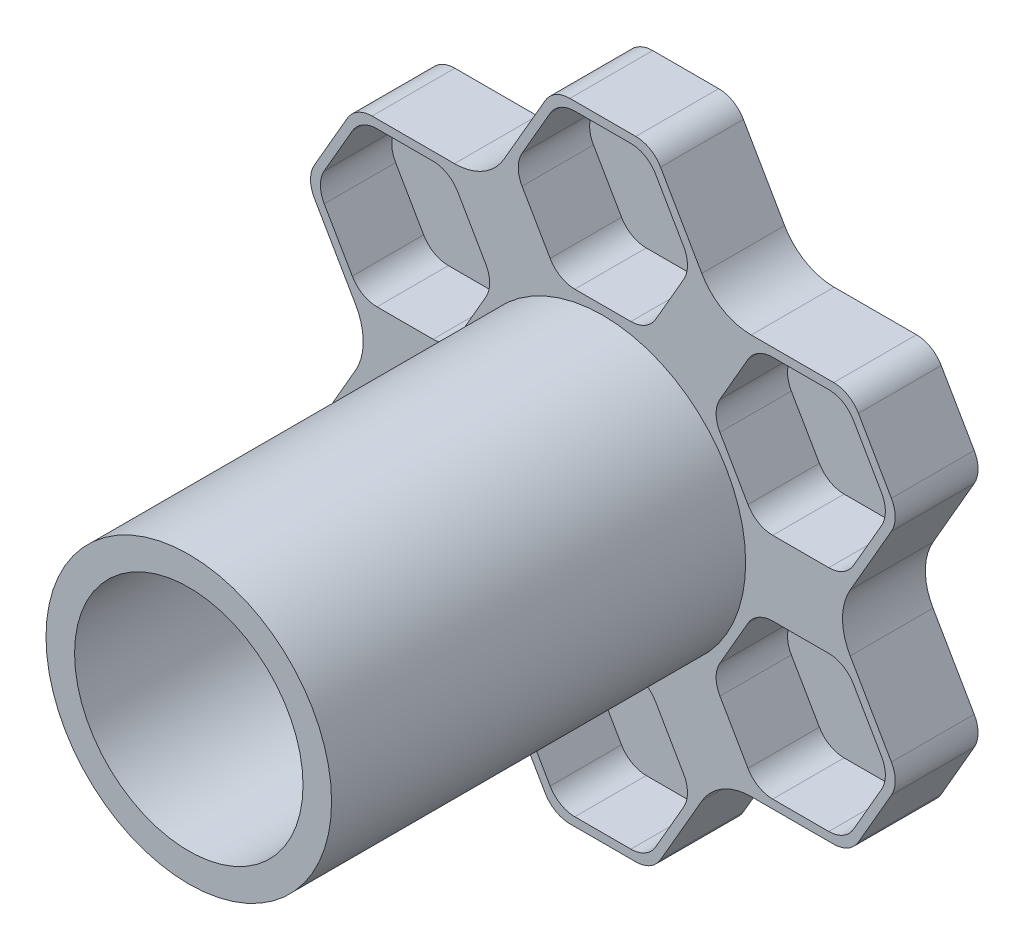
SolidWorks part; units mm, degrees
note: The reader was unsure of these and kept them because the rebuilt part matched: shared geometry of "Base_Sketch<3>", "Base_Sketch<4>", "Base_Sketch<5>", "Base_Sketch<7>".
ref_plane "Front Plane" through (0, 0, 0) normal (0, 0, 1) x (1, 0, 0)
ref_plane "Top Plane" through (0, 0, 0) normal (0, 1, 0) x (1, 0, 0)
ref_plane "Right Plane" through (0, 0, 0) normal (1, 0, 0) x (0, 0, -1)
sketch "Base_Sketch" plane through (0, 0, 0) normal (0, 0, 1) x (1, 0, 0)
  line L0 (0, 38.7616) -> (0, -17.7739) construction
  line L1 (-17.446, 0) -> (12.0679, 0) construction
  line L2 (-15.5885, 107) -> (-31.1769, 80)
  line L3 (34.641, 80) -> (17.3205, 110)
  line L4 (17.3205, 110) -> (-17.3205, 110)
  line L5 (-17.3205, 110) -> (-34.641, 80)
  line L6 (-34.641, 80) -> (-17.3205, 50)
  line L7 (-17.3205, 50) -> (17.3205, 50)
  line L8 (17.3205, 50) -> (34.641, 80)
  line L9 (-31.1769, 80) -> (-15.5885, 53)
  line L10 (-15.5885, 53) -> (15.5885, 53)
  line L11 (15.5885, 53) -> (31.1769, 80)
  line L12 (31.1769, 80) -> (15.5885, 107)
  line L13 (15.5885, 107) -> (-15.5885, 107)
  line L14 (51.9615, 70) -> (34.641, 40)
  line L15 (53.6936, 67) -> (38.1051, 40)
  line L16 (34.641, 40) -> (51.9615, 10)
  line L17 (51.9615, 10) -> (86.6025, 10)
  line L18 (86.6025, 10) -> (103.923, 40)
  line L19 (53.6936, 13) -> (84.8705, 13)
  line L20 (38.1051, 40) -> (53.6936, 13)
  line L21 (84.8705, 67) -> (53.6936, 67)
  line L22 (100.4589, 40) -> (84.8705, 67)
  line L23 (84.8705, 13) -> (100.4589, 40)
  line L24 (103.923, 40) -> (86.6025, 70)
  line L25 (86.6025, 70) -> (51.9615, 70)
  line L26 (86.6025, -10) -> (51.9615, -10)
  line L27 (84.8705, -13) -> (53.6936, -13)
  line L28 (51.9615, -10) -> (34.641, -40)
  line L29 (34.641, -40) -> (51.9615, -70)
  line L30 (51.9615, -70) -> (86.6025, -70)
  line L31 (38.1051, -40) -> (53.6936, -67)
  line L32 (53.6936, -13) -> (38.1051, -40)
  line L33 (100.4589, -40) -> (84.8705, -13)
  line L34 (84.8705, -67) -> (100.4589, -40)
  line L35 (53.6936, -67) -> (84.8705, -67)
  line L36 (86.6025, -70) -> (103.923, -40)
  line L37 (103.923, -40) -> (86.6025, -10)
  line L38 (34.641, -80) -> (17.3205, -50)
  line L39 (31.1769, -80) -> (15.5885, -53)
  line L40 (17.3205, -50) -> (-17.3205, -50)
  line L41 (-17.3205, -50) -> (-34.641, -80)
  line L42 (-34.641, -80) -> (-17.3205, -110)
  line L43 (-15.5885, -53) -> (-31.1769, -80)
  line L44 (15.5885, -53) -> (-15.5885, -53)
  line L45 (15.5885, -107) -> (31.1769, -80)
  line L46 (-15.5885, -107) -> (15.5885, -107)
  line L47 (-31.1769, -80) -> (-15.5885, -107)
  line L48 (-17.3205, -110) -> (17.3205, -110)
  line L49 (17.3205, -110) -> (34.641, -80)
  line L50 (-51.9615, -70) -> (-34.641, -40)
  line L51 (-53.6936, -67) -> (-38.1051, -40)
  line L52 (-34.641, -40) -> (-51.9615, -10)
  line L53 (-51.9615, -10) -> (-86.6025, -10)
  line L54 (-86.6025, -10) -> (-103.923, -40)
  line L55 (-53.6936, -13) -> (-84.8705, -13)
  line L56 (-38.1051, -40) -> (-53.6936, -13)
  line L57 (-84.8705, -67) -> (-53.6936, -67)
  line L58 (-100.4589, -40) -> (-84.8705, -67)
  line L59 (-84.8705, -13) -> (-100.4589, -40)
  line L60 (-103.923, -40) -> (-86.6025, -70)
  line L61 (-86.6025, -70) -> (-51.9615, -70)
  line L62 (-86.6025, 10) -> (-51.9615, 10)
  line L63 (-84.8705, 13) -> (-53.6936, 13)
  line L64 (-51.9615, 10) -> (-34.641, 40)
  line L65 (-34.641, 40) -> (-51.9615, 70)
  line L66 (-51.9615, 70) -> (-86.6025, 70)
  line L67 (-38.1051, 40) -> (-53.6936, 67)
  line L68 (-53.6936, 13) -> (-38.1051, 40)
  line L69 (-100.4589, 40) -> (-84.8705, 13)
  line L70 (-84.8705, 67) -> (-100.4589, 40)
  line L71 (-53.6936, 67) -> (-84.8705, 67)
  line L72 (-86.6025, 70) -> (-103.923, 40)
  line L73 (-103.923, 40) -> (-86.6025, 10)
  circle A0 centre (0, 0) radius 50
  circle A1 centre (0, 80) radius 30 construction
  arc A3 (34.641, 80) -> (51.9615, 70) centre (51.9615, 90) ccw
  circle A4 centre (69.282, 40) radius 30 construction
  arc A5 (86.6025, 10) -> (86.6025, -10) centre (103.923, 0) ccw
  circle A6 centre (69.282, -40) radius 30 construction
  arc A7 (51.9615, -70) -> (34.641, -80) centre (51.9615, -90) ccw
  circle A8 centre (0, -80) radius 30 construction
  arc A9 (-34.641, -80) -> (-51.9615, -70) centre (-51.9615, -90) ccw
  circle A10 centre (-69.282, -40) radius 30 construction
  arc A11 (-86.6025, -10) -> (-86.6025, 10) centre (-103.923, 0) ccw
  circle A12 centre (-69.282, 40) radius 30 construction
  arc A13 (-51.9615, 70) -> (-34.641, 80) centre (-51.9615, 90) ccw
  circle A14 centre (0, 0) radius 40
  circle A15 centre (0, 0) radius 10
  point P18 (0, 50)
  point P36 (43.3013, 25)
  point P53 (43.3013, -25)
  point P70 (0, -50)
  point P87 (-43.3013, -25)
  point P104 (-43.3013, 25)
  point P111 (0, 0)
  dimension "D1" = 100
  dimension "D3" = 60
  dimension "D5" = 10
  dimension "D6" = 20
  dimension "D2" = 3
  dimension "D4" = 6
extrude "Boss-Extrude2" add sketch "Base_Sketch" against normal blind 4 contours L55 L59 L58 L57 L51 L56 | L31 L35 L34 L33 L27 L32 | L43 L47 L46 L45 L39 L44 | A7 L29 L28 A0 L40 L38 | L48 L49 L38 L40 L41 L42 L47 L43 L44 L39 L45 L46 | L36 L37 L26 L28 L29 L30 L35 L31 L32 L27 L33 L34 | A5 L17 L16 A0 L28 L26 | L24 L25 L14 L16 L17 L18 L23 L19 L20 L15 L21 L22 | L19 L23 L22 L21 L15 L20 | L12 L13 L2 L9 L10 L11 | L7 L8 L3 L4 L5 L6 L13 L12 L11 L10 L9 L2 | L72 L73 L62 L64 L65 L66 L71 L67 L68 L63 L69 L70 | A13 L65 L64 A0 L7 L6 | A11 L53 L52 A0 L64 L62 | A9 L41 L40 A0 L52 L50 | L60 L61 L50 L52 L53 L54 L59 L55 L56 L51 L57 L58 | L67 L71 L70 L69 L63 L68 | A3 L8 L7 A0 L16 L14
extrude "Boss-Extrude3" add sketch "Base_Sketch<3>" along normal blind 25 from surface at 0 contours A0 A14 | A15 | L60 L61 L50 L52 L53 L54 L59 L55 L56 L51 L57 L58 | A9 L41 L40 A0 L52 L50 | L48 L49 L38 L40 L41 L42 L47 L43 L44 L39 L45 L46 | A7 L29 L28 A0 L40 L38 | L31 L35 L34 L33 L27 L32 | L36 L37 L26 L28 L29 L30 L35 L31 L32 L27 L33 L34 | A5 L17 L16 A0 L28 L26 | L24 L25 L14 L16 L17 L18 L23 L19 L20 L15 L21 L22 | A3 L8 L7 A0 L16 L14 | L7 L8 L3 L4 L5 L6 L13 L12 L11 L10 L9 L2 | A13 L65 L64 A0 L7 L6 | L72 L73 L62 L64 L65 L66 L71 L67 L68 L63 L69 L70 | A11 L53 L52 A0 L64 L62 | A14 A15
sketch "Base_Sketch<3>" plane through (0, 0, 0) normal (0, 0, 1) x (1, 0, 0) same geometry as "Base_Sketch"
extrude "Boss-Extrude4" add sketch "Base_Sketch<4>" along normal blind 40 from surface at 25 contours A0 A14 | A14 A15 | A15 starting at face at (69.282, -40, 25)
sketch "Base_Sketch<4>" plane through (0, 0, 0) normal (0, 0, 1) x (1, 0, 0) same geometry as "Base_Sketch"
extrude "Boss-Extrude5" add sketch "Base_Sketch<5>" along normal blind 5 from surface at 65 contours A0 A14 | A14 A15 | A15 starting at face at (50, 0, 65)
sketch "Base_Sketch<5>" plane through (0, 0, 0) normal (0, 0, 1) x (1, 0, 0) same geometry as "Base_Sketch"
extrude "Boss-Extrude6" add sketch "Base_Sketch<7>" along normal blind 100 from surface at 70 contours A0 A14 starting at face at (50, 0, 70)
sketch "Base_Sketch<7>" plane through (0, 0, 0) normal (0, 0, 1) x (1, 0, 0) same geometry as "Base_Sketch"
fillet "Fillet1" radius 10 8 edges at (-31.1769, 80, 12.5) (-15.5885, 53, 12.5) (15.5885, 53, 12.5) (17.3205, 110, 10.5) (-17.3205, 110, 10.5) (15.5885, 107, 12.5) (31.1769, 80, 12.5) (-15.5885, 107, 12.5)
fillet "Fillet2" radius 10 40 edges at (86.6025, 70, 10.5) (103.923, 40, 10.5) (103.923, -40, 10.5) (86.6025, -70, 10.5) (17.3205, -110, 10.5) (-17.3205, -110, 10.5) (-86.6025, -70, 10.5) (-103.923, -40, 10.5) (-103.923, 40, 10.5) (-86.6025, 70, 10.5) (84.8705, -13, 12.5) (53.6936, -13, 12.5) (38.1051, -40, 12.5) (53.6936, -67, 12.5) (84.8705, -67, 12.5) (100.4589, -40, 12.5) (100.4589, 40, 12.5) (84.8705, 67, 12.5) (53.6936, 67, 12.5) (38.1051, 40, 12.5) (53.6936, 13, 12.5) (84.8705, 13, 12.5) (-84.8705, 67, 12.5) (-100.4589, 40, 12.5) (-84.8705, 13, 12.5) (-38.1051, 40, 12.5) (-53.6936, 67, 12.5) (-100.4589, -40, 12.5) (-84.8705, -67, 12.5) (-53.6936, -67, 12.5) (-38.1051, -40, 12.5) (-53.6936, -13, 12.5) (-84.8705, -13, 12.5) (-15.5885, -107, 12.5) (15.5885, -107, 12.5) (31.1769, -80, 12.5) (15.5885, -53, 12.5) (-15.5885, -53, 12.5) (-31.1769, -80, 12.5) (-53.6936, 13, 12.5)
